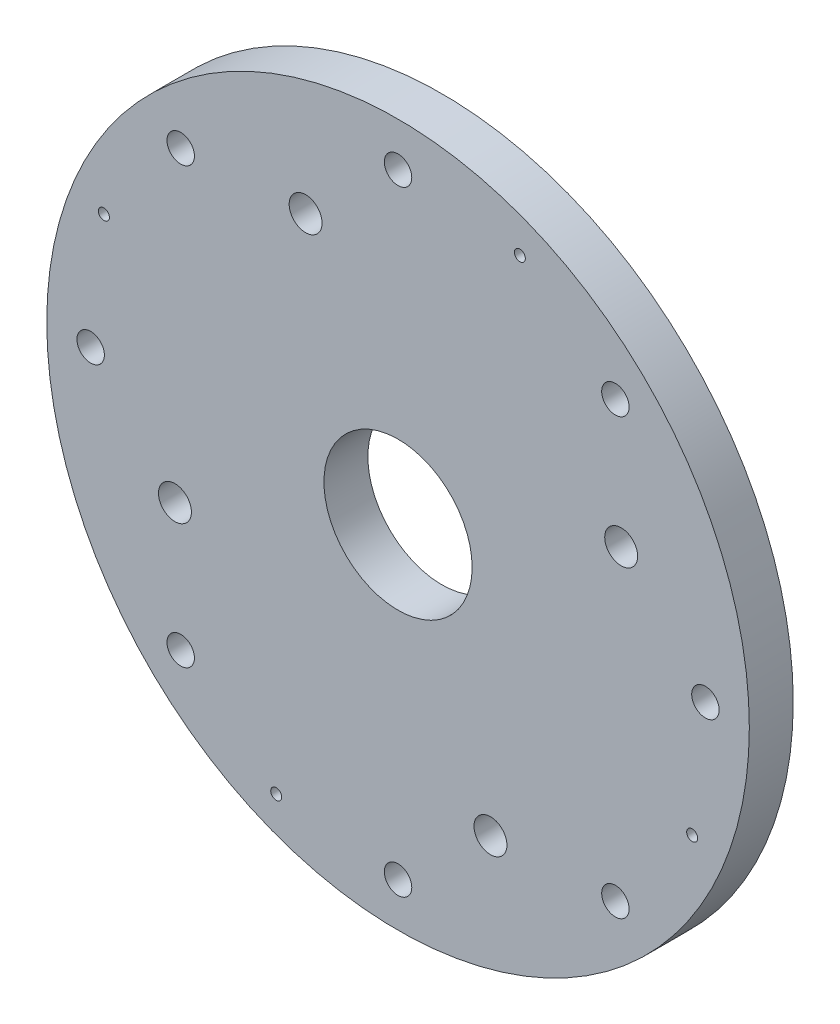
SolidWorks part; units mm, degrees
ref_plane "Alzado" through (0, 0, 0) normal (0, 0, 1) x (1, 0, 0)
ref_plane "Planta" through (0, 0, 0) normal (0, 1, 0) x (1, 0, 0)
ref_plane "Vista lateral" through (0, 0, 0) normal (1, 0, 0) x (0, 0, -1)
sketch "Croquis1" plane through (0, 0, 0) normal (0, 0, 1) x (1, 0, 0)
  circle A0 centre (0, 0) radius 32
  dimension "D1" = 64
extrude "Saliente-Extruir1" add sketch "Croquis1" along normal blind 4
sketch "Croquis2" plane through (0, 0, 4) normal (0, 0, 1) x (1, 0, 0)
  line L0 (0, 0) -> (0, 28) construction
  line L1 (0, 0) -> (19.799, 19.799) construction
  line L2 (0, 0) -> (28, 0) construction
  line L3 (0, 0) -> (19.799, -19.799) construction
  line L4 (0, 0) -> (0, -28) construction
  line L5 (0, 0) -> (-19.799, -19.799) construction
  line L6 (0, 0) -> (-28, 0) construction
  line L7 (0, 0) -> (-19.799, 19.799) construction
  circle A0 centre (0, 28) radius 1.25
  circle A1 centre (0, 0) radius 32 construction
  circle A2 centre (19.799, 19.799) radius 1.25
  circle A3 centre (28, 0) radius 1.25
  circle A4 centre (19.799, -19.799) radius 1.25
  circle A5 centre (0, -28) radius 1.25
  circle A6 centre (-19.799, -19.799) radius 1.25
  circle A7 centre (-28, 0) radius 1.25
  circle A8 centre (-19.799, 19.799) radius 1.25
  point P19 (0, 0)
  dimension "D1" = 2.5
  dimension "D2" = 28
  dimension "D3" = 8
extrude "Cortar-Extruir1" cut sketch "Croquis2" against normal through all
sketch "Croquis3" plane through (0, 0, 4) normal (0, 0, 1) x (1, 0, 0)
  circle A0 centre (0, 0) radius 6.75
  dimension "D1" = 13.5
extrude "Cortar-Extruir2" cut sketch "Croquis3" against normal blind 10
sketch "Croquis4" plane through (0, 0, 0) normal (0, 0, -1) x (-1, 0, 0)
  line L0 (-19.799, 19.799) -> (0, 28) construction
  line L1 (-9.8995, 23.8995) -> (-12.2459, 29.5641) construction
  line L2 (-12.2459, 29.5641) -> (-11.0978, 26.7925) construction
  circle A1 centre (0, 0) radius 32 construction
  circle A2 centre (-11.0978, 26.7925) radius 0.5
  circle A3 centre (0, 0) radius 32 construction
  circle A4 centre (26.7925, 11.0978) radius 0.5
  circle A5 centre (11.0978, -26.7925) radius 0.5
  circle A6 centre (-26.7925, -11.0978) radius 0.5
  point P9 (-9.8995, 23.8995)
  point P31 (0, 0)
  dimension "D1" = 1
  dimension "D2" = 3
  dimension "D3" = 4
extrude "Cortar-Extruir3" cut sketch "Croquis4" against normal blind 10
sketch "Croquis5" plane through (0, 0, 0) normal (0, 0, -1) x (-1, 0, 0)
  line L0 (0, 28) -> (19.799, 19.799) construction
  line L1 (9.8995, 23.8995) -> (12.2459, 29.5641) construction
  line L2 (12.2459, 29.5641) -> (8.419, 20.3253) construction
  circle A0 centre (0, 0) radius 32 construction
  circle A1 centre (8.419, 20.3253) radius 1.5
  circle A2 centre (20.3253, -8.419) radius 1.5
  circle A3 centre (-8.419, -20.3253) radius 1.5
  circle A4 centre (-20.3253, 8.419) radius 1.5
  point P19 (0, 0)
  dimension "D1" = 3
  dimension "D2" = 10
  dimension "D3" = 4
extrude "Cortar-Extruir4" cut sketch "Croquis5" against normal blind 10
sketch "Croquis6" plane through (0, 0, 0) normal (0, 0, 1) x (1, 0, 0)
  line L0 (-26.7925, 11.0978) -> (0, 0) construction
  line L1 (6.5713, 21.0907) -> (10.2668, 19.56)
  line L2 (-21.0907, 6.5713) -> (-17.3952, 5.0405)
  line L3 (-21.0907, 6.5713) -> (-19.56, 10.2668)
  line L4 (-19.56, 10.2668) -> (-15.8645, 8.7361)
  line L5 (-17.3952, 5.0405) -> (-15.8645, 8.7361)
  line L6 (-21.0907, 6.5713) -> (-15.8645, 8.7361) construction
  line L7 (-19.56, 10.2668) -> (-17.3952, 5.0405) construction
  line L8 (6.5713, 21.0907) -> (5.0405, 17.3952)
  line L9 (5.0405, 17.3952) -> (8.7361, 15.8645)
  line L10 (10.2668, 19.56) -> (8.7361, 15.8645)
  line L11 (21.0907, -6.5713) -> (19.56, -10.2668)
  line L12 (21.0907, -6.5713) -> (17.3952, -5.0405)
  line L13 (17.3952, -5.0405) -> (15.8645, -8.7361)
  line L14 (19.56, -10.2668) -> (15.8645, -8.7361)
  line L15 (-6.5713, -21.0907) -> (-10.2668, -19.56)
  line L16 (-6.5713, -21.0907) -> (-5.0405, -17.3952)
  line L17 (-5.0405, -17.3952) -> (-8.7361, -15.8645)
  line L18 (-10.2668, -19.56) -> (-8.7361, -15.8645)
  point P4 (-18.4776, 7.6537)
  point P24 (0, 0)
  dimension "D1" = 4
  dimension "D2" = 4
  dimension "D3" = 20
  dimension "D4" = 4
extrude "Saliente-Extruir3" [suppressed] add sketch "Croquis6" against normal blind 5
sketch "Croquis7" [suppressed] plane through (-8.419, -20.3253, 0) normal (-0.3827, -0.9239, 0) x (0.9239, -0.3827, 0)
  line L0 (0, 0) -> (0, -5) construction
  line L1 (-2, -5) -> (2, -5) construction
  circle A0 centre (0, -2.5) radius 0.75
  point P9 (0, -2.5)
  dimension "D1" = 1.5
extrude "Cortar-Extruir5" [suppressed] cut sketch "Croquis7" against normal through all
pattern_circular "MatrizC1" [suppressed] count 4 over 360 of bodies 109
